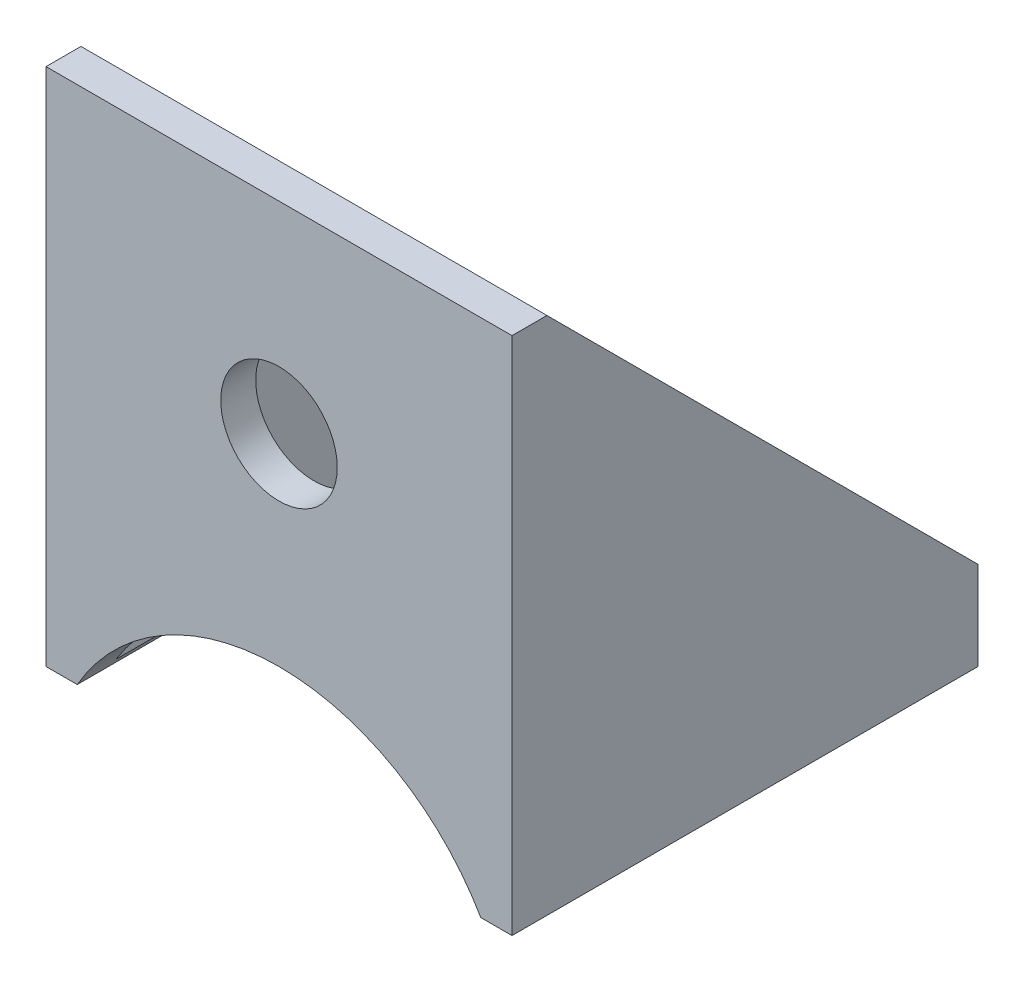
SolidWorks part; units mm, degrees
ref_plane "Front Plane" through (0, 0, 0) normal (0, 0, 1) x (1, 0, 0)
ref_plane "Top Plane" through (0, 0, 0) normal (0, 1, 0) x (1, 0, 0)
ref_plane "Right Plane" through (0, 0, 0) normal (1, 0, 0) x (0, 0, -1)
sketch "Sketch1" plane through (0, 0, 0) normal (0, 1, 0) x (1, 0, 0)
  line L0 (-12.7, 12.7) -> (-12.7, -12.7)
  line L1 (-12.7, -12.7) -> (12.7, -12.7)
  line L2 (12.7, -12.7) -> (12.7, 12.7)
  line L3 (12.7, 12.7) -> (10.795, 12.7)
  line L4 (10.795, 12.7) -> (10.795, -10.795)
  line L5 (10.795, -10.795) -> (-10.795, -10.795)
  line L6 (-10.795, -10.795) -> (-10.795, 12.7)
  line L7 (-10.795, 12.7) -> (-12.7, 12.7)
  point P10 (-12.7, 0)
  point P12 (0, -10.795)
  dimension "D1" = 1.905
  dimension "D2" = 1.905
  dimension "D3" = 1.905
  dimension "D4" = 25.4
  dimension "D5" = 25.4
extrude "Boss-Extrude1" add sketch "Sketch1" along normal blind 34.671
sketch "Sketch2" plane through (-12.7, 0, 0) normal (-1, 0, 0) x (0, 0, 1)
  line L0 (-12.7, 11.176) -> (10.795, 34.671)
  line L1 (-12.7, 34.671) -> (12.7, 34.671) construction
  line L2 (12.7, 34.671) -> (12.7, 0) construction
  line L3 (10.795, 34.671) -> (-12.7, 34.671)
  line L6 (-12.7, 34.671) -> (-12.7, 11.176)
  dimension "D1" = 1.905
  dimension "D2" = 45
extrude "Cut-Extrude1" cut sketch "Sketch2" against normal through all
sketch "Sketch3" plane through (0, 0, 12.7) normal (0, 0, 1) x (1, 0, 0)
  line L1 (-12.7, 12.7) -> (12.7, 12.7) construction
  line L2 (-12.7, 34.671) -> (-12.7, 0) construction
  line L3 (12.7, 34.671) -> (12.7, 0) construction
  line L4 (-12.7, 34.671) -> (12.7, 34.671) construction
  circle A0 centre (0, 23.6855) radius 3.175
  dimension "D1" = 6.35
  dimension "D2" = 21.971
  dimension "D3" = 10.9855
extrude "Cut-Extrude2" cut sketch "Sketch3" against normal through all
sketch "Sketch4" plane through (0, 0, 12.7) normal (0, 0, 1) x (1, 0, 0)
  line L0 (-12.7, 0) -> (12.7, 0) construction
  line L1 (-12.7, 0) -> (12.7, 0)
  line L2 (-10.9985, 6.35) -> (-12.7, 6.35)
  line L3 (-12.7, 34.671) -> (-12.7, 0) construction
  line L4 (-12.7, 6.35) -> (-12.7, 0)
  line L5 (10.9985, 6.35) -> (12.7, 6.35)
  line L6 (12.7, 34.671) -> (12.7, 0) construction
  line L7 (12.7, 6.35) -> (12.7, 0)
  arc A0 (10.9985, 6.35) -> (-10.9985, 6.35) centre (0, 0) ccw
  dimension "D1" = 6.35
extrude "Cut-Extrude3" cut sketch "Sketch4" against normal through all
